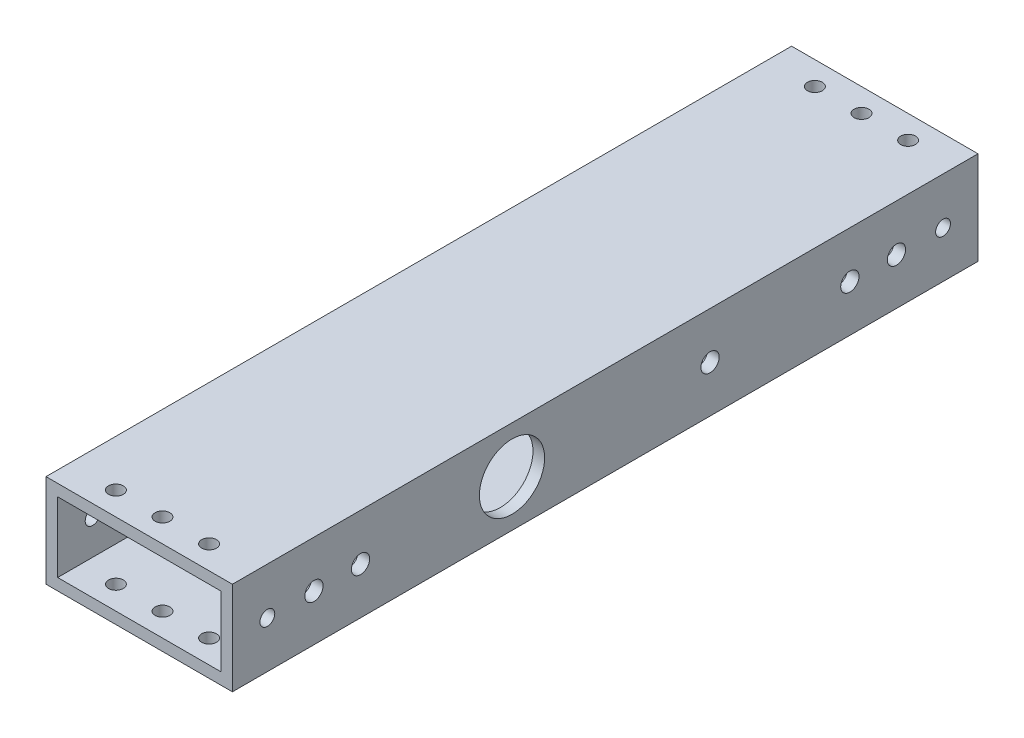
SolidWorks part; units mm, degrees
material "6061-T6 (SS)"
ref_plane "Front Plane" through (0, 0, 0) normal (0, 0, 1) x (1, 0, 0)
ref_plane "Top Plane" through (0, 0, 0) normal (0, 1, 0) x (1, 0, 0)
ref_plane "Right Plane" through (0, 0, 0) normal (1, 0, 0) x (0, 0, -1)
sketch "Sketch1" plane through (0, 0, 0) normal (0, 0, 1) x (1, 0, 0)
  line L0 (-22.225, 9.525) -> (22.225, 9.525)
  line L1 (-25.4, -12.7) -> (25.4, -12.7)
  line L2 (-25.4, -12.7) -> (-25.4, 12.7)
  line L3 (-25.4, 12.7) -> (25.4, 12.7)
  line L4 (25.4, -12.7) -> (25.4, 12.7)
  line L5 (-25.4, -12.7) -> (25.4, 12.7) construction
  line L6 (-25.4, 12.7) -> (25.4, -12.7) construction
  line L7 (22.225, -9.525) -> (22.225, 9.525)
  line L8 (-22.225, -9.525) -> (22.225, -9.525)
  line L9 (-22.225, -9.525) -> (-22.225, 9.525)
  point P0 (0, 0)
  dimension "D1" = 50.8
  dimension "D2" = 25.4
  dimension "D3" = 3.175
extrude "Boss-Extrude1" add sketch "Sketch1" along normal mid plane 203.2
sketch "Sketch2" plane through (25.4, 0, 0) normal (1, 0, 0) x (0, 0, -1)
  line L0 (-101.6, -12.7) -> (-101.6, 12.7) construction
  line L1 (0, 12.7) -> (0, -12.7) construction
  line L2 (-101.6, 12.7) -> (101.6, 12.7) construction
  line L3 (-101.6, -12.7) -> (101.6, -12.7) construction
  circle A0 centre (-92.075, 0) radius 2.0193
  circle A1 centre (92.075, 0) radius 2.0193
  circle A2 centre (-79.375, 0) radius 2.4892
  circle A3 centre (-66.675, 0) radius 2.4892
  circle A4 centre (66.675, 0) radius 2.4892
  circle A5 centre (79.375, 0) radius 2.4892
  dimension "D2" = 4.0386
  dimension "D5" = 4.9784
  dimension "D1" = 9.525
  dimension "D3" = 12.7
  dimension "D4" = 12.7
extrude "Cut-Extrude1" cut sketch "Sketch2" against normal through all
sketch "Sketch3" plane through (0, 12.7, 0) normal (0, 1, 0) x (1, 0, 0)
  line L0 (-25.4, 0) -> (25.4, 0) construction
  line L1 (-25.4, -101.6) -> (-25.4, 101.6) construction
  line L2 (25.4, -101.6) -> (25.4, 101.6) construction
  line L3 (25.4, -101.6) -> (-25.4, -101.6) construction
  circle A0 centre (-12.7, -95.25) radius 2.0193
  circle A1 centre (0, -95.25) radius 2.0193
  circle A2 centre (12.7, -95.25) radius 2.0193
  circle A3 centre (12.7, 95.25) radius 2.0193
  circle A4 centre (0, 95.25) radius 2.0193
  circle A5 centre (-12.7, 95.25) radius 2.0193
  dimension "D1" = 4.0386
  dimension "D2" = 12.7
  dimension "D3" = 12.7
  dimension "D4" = 6.35
extrude "Cut-Extrude2" cut sketch "Sketch3" against normal through all
sketch "Sketch4" plane through (25.4, 0, 0) normal (1, 0, 0) x (0, 0, -1)
  line L0 (-25.4, 0) -> (-66.675, 0) construction
  line L1 (-16.51, 0) -> (-34.29, 0) construction
  line L7 (101.6, -12.7) -> (101.6, 12.7) construction
  line L8 (-25.4, 0) -> (28.575, 0) construction
  circle A0 centre (-25.4, 0) radius 8.89
  circle A5 centre (-66.675, 0) radius 2.4892
  circle A7 centre (-66.675, 0) radius 2.4892 construction
  circle A8 centre (-79.375, 0) radius 2.4892 construction
  circle A9 centre (28.575, 0) radius 2.4892
  dimension "D2" = 17.78
  dimension "D1" = 53.975
  dimension "5" = 127
extrude "Cut-Extrude3" cut sketch "Sketch4" against normal through all contours A0 | A5 | A9
sketch "Sketch5" plane through (0, -12.7, 0) normal (0, -1, 0) x (1, 0, 0)
  line L0 (-25.4, 101.6) -> (-25.4, -101.6) construction
  line L1 (-25.4, 101.6) -> (25.4, 101.6) construction
  line L2 (-16.51, -12.7) -> (-3.81, -12.7) construction
  line L3 (-16.51, -12.7) -> (-16.51, 0) construction
  circle A0 centre (-3.81, 63.5) radius 2.5527
  circle A1 centre (-16.51, 63.5) radius 2.5527
  circle A2 centre (-16.51, 50.8) radius 2.5527
  circle A3 centre (-3.81, 50.8) radius 2.5527
  circle A4 centre (-16.51, -12.7) radius 2.5527
  circle A5 centre (-3.81, -12.7) radius 2.5527
  circle A6 centre (-3.81, 0) radius 2.5527
  circle A7 centre (-16.51, 0) radius 2.5527
  point P12 (0, 0)
  point P14 (0, 0)
  point P25 (-16.6679, -7.4048)
  dimension "D3" = 5.1054
  dimension "D4" = 8.89
  dimension "D7" = 12.7
  dimension "D12" = 50.8
  dimension "D5" = 38.1
  dimension "D6" = 12.7
  dimension "D10" = 12.7
  dimension "D11" = 12.7
  dimension "D1" = 2
  dimension "D2" = 2
  dimension "D8" = 2
  dimension "D9" = 2
extrude "Cut-Extrude4" cut sketch "Sketch5" against normal up to next
